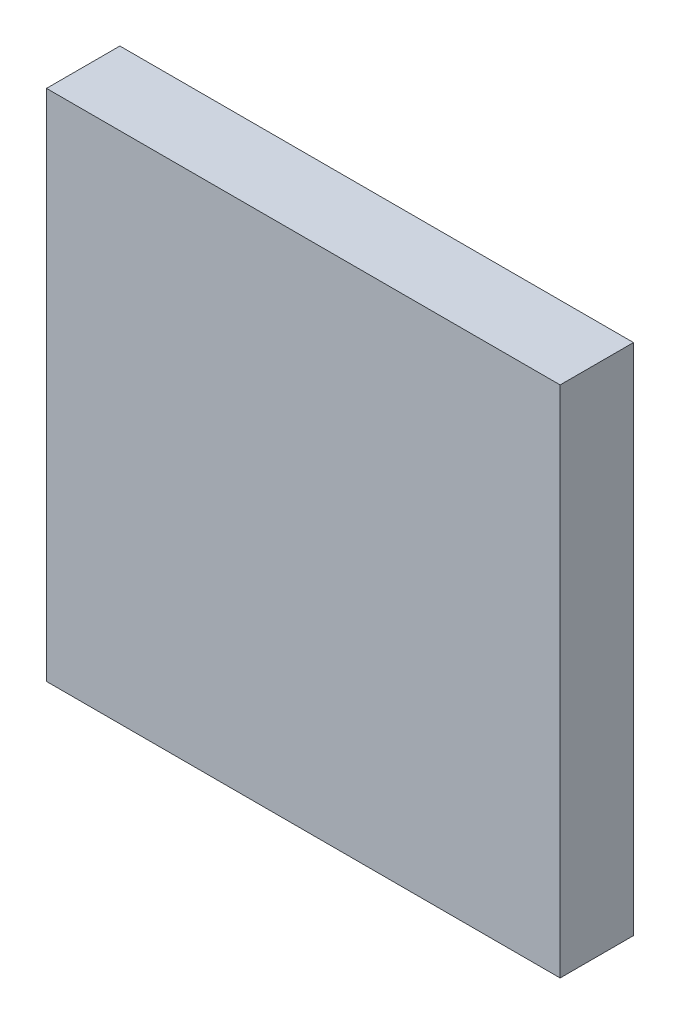
SolidWorks part; units mm, degrees
ref_plane "Front Plane" through (0, 0, 0) normal (0, 0, 1) x (1, 0, 0)
ref_plane "Top Plane" through (0, 0, 0) normal (0, 1, 0) x (1, 0, 0)
ref_plane "Right Plane" through (0, 0, 0) normal (1, 0, 0) x (0, 0, -1)
sketch "Sketch2" plane through (0, 0, 0) normal (0, 0, 1) x (1, 0, 0)
  line L1 (-17.5, -17.5) -> (17.5, -17.5)
  line L2 (-17.5, -17.5) -> (-17.5, 17.5)
  line L3 (-17.5, 17.5) -> (17.5, 17.5)
  line L4 (17.5, -17.5) -> (17.5, 17.5)
  line L5 (-17.5, -17.5) -> (17.5, 17.5) construction
  line L6 (-17.5, 17.5) -> (17.5, -17.5) construction
  point P0 (0, 0)
  dimension "D1" = 35
  dimension "D2" = 35
extrude "Boss-Extrude1" add sketch "Sketch2" along normal blind 5
